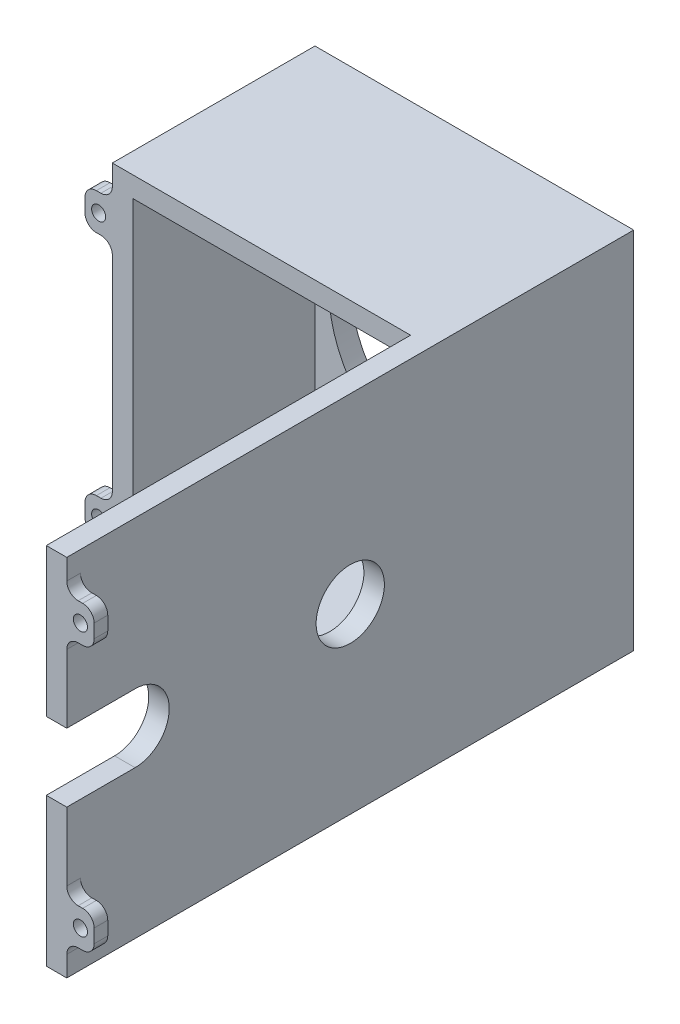
SolidWorks part; units mm, degrees
ref_plane "Front Plane" through (0, 0, 0) normal (1, 0, 0) x (0, 1, 0)
ref_plane "Top Plane" through (0, 0, 0) normal (0, 0, 1) x (0, 1, 0)
ref_plane "Right Plane" through (0, 0, 0) normal (0, 1, 0) x (-1, 0, 0)
sketch "Sketch1" plane through (0, 0, 0) normal (0, 0, 1) x (0, 1, 0)
  line L1 (-40, -35) -> (40, -35)
  line L2 (-40, -35) -> (-40, 35)
  line L3 (-40, 35) -> (40, 35)
  line L4 (40, -35) -> (40, 35)
  line L5 (-40, -35) -> (40, 35) construction
  line L6 (-40, 35) -> (40, -35) construction
  point P0 (0, 0)
  dimension "D1" = 80
  dimension "D2" = 70
extrude "Boss-Extrude1" add sketch "Sketch1" along normal blind 4.5
sketch "Sketch2" plane through (0, 0, 4.5) normal (0, 0, 1) x (1, 0, 0)
  line L0 (35, 40) -> (-35, 40) construction
  line L1 (35, -40) -> (30.5, -40)
  line L2 (35, -40) -> (35, 40)
  line L3 (35, 40) -> (30.5, 40)
  line L4 (30.5, -40) -> (30.5, 40)
  dimension "D1" = 4.5
extrude "Boss-Extrude2" add sketch "Sketch2" along normal blind 120
sketch "Sketch3" plane through (0, 0, 4.5) normal (0, 0, 1) x (1, 0, 0)
  line L0 (30.5, 40) -> (-35, 40)
  line L1 (-35, 40) -> (-35, -40)
  line L2 (-35, -40) -> (30.5, -40)
  line L3 (30.5, -40) -> (30.5, -35.5)
  line L4 (30.5, 40) -> (30.5, -40) construction
  line L5 (30.5, -35.5) -> (-30.5, -35.5)
  line L6 (-30.5, -35.5) -> (-30.5, 35.5)
  line L7 (-30.5, 35.5) -> (30.5, 35.5)
  line L8 (30.5, 35.5) -> (30.5, 40)
  dimension "D1" = 4.5
  dimension "D2" = 4.5
extrude "Boss-Extrude3" add sketch "Sketch3" along normal blind 40
sketch "Sketch4" plane through (0, 0, 0) normal (0, 0, -1) x (1, 0, 0)
  circle A0 centre (0, 0) radius 27.5
  dimension "D1" = 55
extrude "Cut-Extrude1" cut sketch "Sketch4" against normal up to next
sketch "Sketch5" plane through (30.5, 0, 0) normal (-1, 0, 0) x (0, -1, 0)
  line L0 (0, 124.5) -> (0, 0) construction
  line L1 (-40, 124.5) -> (40, 124.5) construction
  line L3 (-7.5, 124.5) -> (7.5, 124.5)
  line L4 (7.5, 124.5) -> (7.5, 109.5)
  line L5 (-7.5, 109.5) -> (-7.5, 124.5)
  line L6 (-40, 0) -> (40, 0) construction
  arc A0 (7.5, 109.5) -> (-7.5, 109.5) centre (0, 109.5) cw
  circle A1 centre (0, 62.25) radius 7.5
  dimension "D2" = 15
  dimension "D3" = 15
  dimension "D1" = 15
extrude "Cut-Extrude2" cut sketch "Sketch5" against normal up to next
sketch "Sketch6" plane through (0, 0, 124.5) normal (0, 0, 1) x (1, 0, 0)
  line L0 (30.5, 0) -> (35, 0) construction
  line L1 (30.5, 35.5) -> (30.5, -35.5) construction
  line L2 (35, -7.5) -> (35, 7.5) construction
  line L3 (35, 7.5) -> (35, 40) construction
  line L4 (35, 33) -> (41, 33)
  line L5 (35, 33) -> (35, 25)
  line L6 (35, 25) -> (41, 25)
  line L7 (41, 33) -> (41, 25)
  line L8 (35, -25) -> (41, -25)
  line L9 (41, -33) -> (41, -25)
  line L10 (35, -33) -> (41, -33)
  line L11 (35, -33) -> (35, -25)
  dimension "D1" = 25
  dimension "D2" = 8
  dimension "D3" = 6
extrude "Boss-Extrude4" add sketch "Sketch6" against normal blind 3
sketch "Sketch7" plane through (0, 0, 44.5) normal (0, 0, 1) x (1, 0, 0)
  line L0 (-35, 0) -> (-30.5, 0) construction
  line L1 (-35, 40) -> (-35, -40) construction
  line L2 (-30.5, -35.5) -> (-30.5, 35.5) construction
  line L3 (-35, -25) -> (-41, -25)
  line L4 (-35, 33) -> (-41, 33)
  line L5 (-35, 33) -> (-35, 25)
  line L6 (-35, 25) -> (-41, 25)
  line L7 (-41, 33) -> (-41, 25)
  line L8 (-41, -33) -> (-41, -25)
  line L9 (-35, -33) -> (-41, -33)
  line L10 (-35, -33) -> (-35, -25)
  dimension "D1" = 25
  dimension "D2" = 8
  dimension "D3" = 6
extrude "Boss-Extrude5" add sketch "Sketch7" against normal blind 3
sketch "Sketch8" plane through (0, 0, 44.5) normal (0, 0, 1) x (1, 0, 0)
  line L0 (-38, 33) -> (-38, 25) construction
  line L1 (-35, 33) -> (-41, 33) construction
  line L2 (-41, 25) -> (-35, 25) construction
  line L3 (-38, -25) -> (-38, -33) construction
  line L4 (-35, -25) -> (-41, -25) construction
  line L5 (-41, -33) -> (-35, -33) construction
  line L6 (38, 33) -> (38, 25) construction
  line L7 (41, 33) -> (35, 33) construction
  line L8 (35, 25) -> (41, 25) construction
  line L9 (38, -25) -> (38, -33) construction
  line L10 (41, -25) -> (35, -25) construction
  line L11 (35, -33) -> (41, -33) construction
  circle A0 centre (-38, 29) radius 1.55
  circle A1 centre (38, 29) radius 1.55
  circle A2 centre (38, -29) radius 1.55
  circle A3 centre (-38, -29) radius 1.55
  dimension "D1" = 3.1
extrude "Cut-Extrude4" cut sketch "Sketch8" against normal through all and the other way through all
fillet "Fillet1" radius 2.5 16 edges at (35, 33, 123) (41, 33, 123) (41, 25, 123) (35, 25, 123) (35, -33, 123) (35, -25, 123) (41, -25, 123) (41, -33, 123) (-35, -33, 43) (-41, -33, 43) (-41, -25, 43) (-35, -25, 43) (-35, 33, 43) (-41, 25, 43) (-35, 25, 43) (-41, 33, 43)
